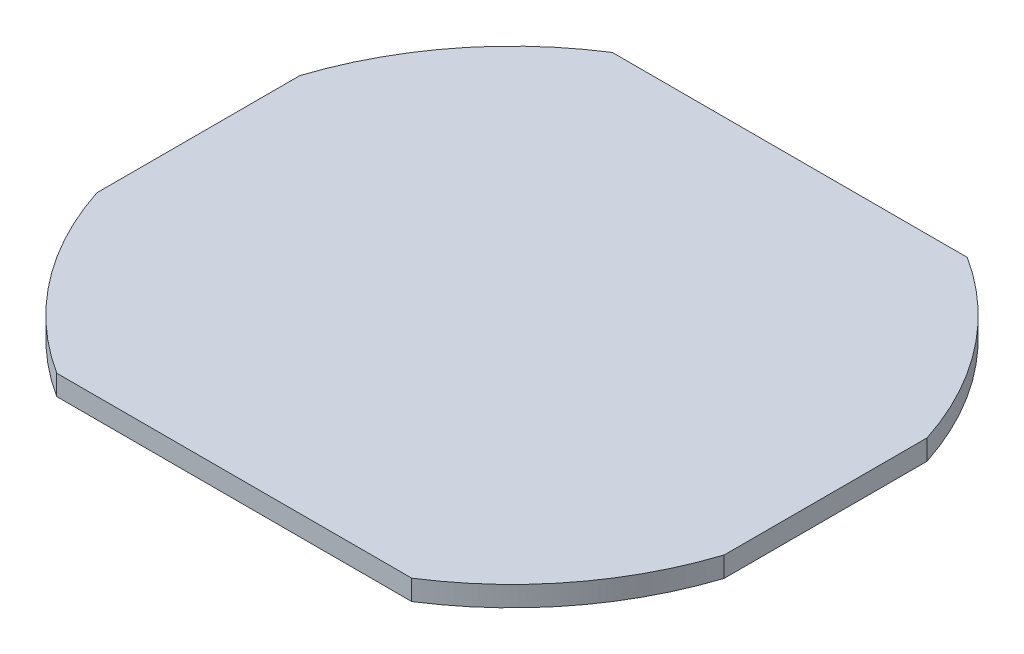
SolidWorks part; units mm, degrees
ref_plane "Front Plane" through (0, 0, 0) normal (0, 0, 1) x (1, 0, 0)
ref_plane "Top Plane" through (0, 0, 0) normal (0, 1, 0) x (1, 0, 0)
ref_plane "Right Plane" through (0, 0, 0) normal (1, 0, 0) x (0, 0, -1)
sketch "Sketch1" plane through (0, 0, 0) normal (0, 1, 0) x (1, 0, 0)
  circle A0 centre (0, 0) radius 32.5
  dimension "D1" = 65
extrude "Boss-Extrude1" add sketch "Sketch1" along normal blind 2
sketch "Sketch2" plane through (0, 2, 0) normal (0, 1, 0) x (1, 0, 0)
  line L0 (17.5, 27.3861) -> (-17.5, 27.3861)
  line L1 (0, 0) -> (-19.5086, 0) construction
  line L2 (17.5, -27.3861) -> (-17.5, -27.3861)
  line L3 (-30.9233, 10) -> (-30.9233, -10)
  line L4 (0, 0) -> (0, -10) construction
  line L5 (30.9233, 10) -> (30.9233, -10)
  arc A0 (17.5, 27.3861) -> (-17.5, 27.3861) centre (0, 0) ccw
  circle A1 centre (0, 0) radius 32.5 construction
  arc A2 (17.5, -27.3861) -> (-17.5, -27.3861) centre (0, 0) cw
  arc A3 (-30.9233, 10) -> (-30.9233, -10) centre (0, 0) ccw
  arc A4 (30.9233, 10) -> (30.9233, -10) centre (0, 0) cw
  point P6 (0, 32.5)
  dimension "D1" = 35
  dimension "D2" = 20
extrude "Cut-Extrude1" cut sketch "Sketch2" against normal up to surface (2 mm away) up to face at (0, 0, 32.5)
